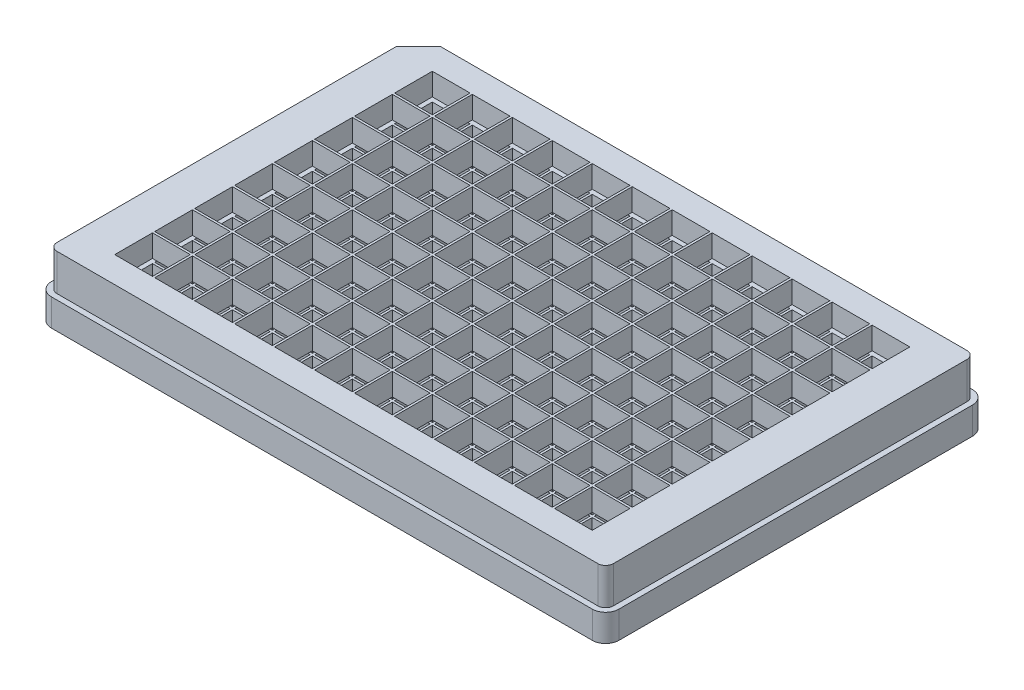
SolidWorks part; units mm, degrees
ref_plane "Front Plane" through (0, 0, 0) normal (0, 0, 1) x (1, 0, 0)
ref_plane "Top Plane" through (0, 0, 0) normal (0, 1, 0) x (1, 0, 0)
ref_plane "Right Plane" through (0, 0, 0) normal (1, 0, 0) x (0, 0, -1)
sketch "Sketch1" plane through (0, 0, 0) normal (0, 1, 0) x (1, 0, 0)
  line L0 (-63.875, -42.8) -> (63.875, 42.8) construction
  line L1 (-63.875, -42.8) -> (63.875, -42.8)
  line L2 (-63.875, -42.8) -> (-63.875, 42.8)
  line L3 (-63.875, 42.8) -> (63.875, 42.8)
  line L4 (63.875, -42.8) -> (63.875, 42.8)
  point P4 (0, 0)
  dimension "D1" = 85.6
  dimension "D2" = 127.75
extrude "Boss-Extrude1" add sketch "Sketch1" along normal blind 14.35
fillet "Fillet1" radius 3 4 edges at (-63.875, 7.175, -42.8) (-63.875, 7.175, 42.8) (63.875, 7.175, 42.8) (63.875, 7.175, -42.8)
sketch "Sketch3" plane through (0, 14.35, 0) normal (0, 1, 0) x (1, 0, 0)
  line L0 (-63.875, 39.8) -> (-63.875, -39.8) construction
  line L1 (60.875, 42.8) -> (-60.875, 42.8) construction
  line L2 (63.875, -39.8) -> (63.875, 39.8) construction
  line L3 (-60.875, -42.8) -> (60.875, -42.8) construction
  line L4 (-63.875, 39.8) -> (-63.875, -39.8)
  line L5 (60.875, 42.8) -> (-60.875, 42.8)
  line L6 (63.875, -39.8) -> (63.875, 39.8)
  line L7 (-60.875, -42.8) -> (60.875, -42.8)
  line L8 (-62.625, 36.6003) -> (-62.625, -39.8)
  line L9 (-60.875, -41.55) -> (60.875, -41.55)
  line L10 (62.625, -39.8) -> (62.625, 39.8)
  line L11 (60.875, 41.55) -> (-57.6753, 41.55)
  line L12 (-62.625, 36.6003) -> (-57.6753, 41.55)
  line L14 (-62.625, 39.8) -> (-62.625, -39.8) construction
  line L15 (60.875, 41.55) -> (-60.875, 41.55) construction
  arc A0 (-60.875, 42.8) -> (-63.875, 39.8) centre (-60.875, 39.8) ccw construction
  arc A1 (63.875, 39.8) -> (60.875, 42.8) centre (60.875, 39.8) ccw construction
  arc A2 (60.875, -42.8) -> (63.875, -39.8) centre (60.875, -39.8) ccw construction
  arc A3 (-63.875, -39.8) -> (-60.875, -42.8) centre (-60.875, -39.8) ccw construction
  arc A4 (-60.875, 42.8) -> (-63.875, 39.8) centre (-60.875, 39.8) ccw
  arc A5 (63.875, 39.8) -> (60.875, 42.8) centre (60.875, 39.8) ccw
  arc A6 (60.875, -42.8) -> (63.875, -39.8) centre (60.875, -39.8) ccw
  arc A7 (-63.875, -39.8) -> (-60.875, -42.8) centre (-60.875, -39.8) ccw
  arc A8 (-62.625, -39.8) -> (-60.875, -41.55) centre (-60.875, -39.8) ccw
  arc A9 (60.875, -41.55) -> (62.625, -39.8) centre (60.875, -39.8) ccw
  arc A10 (62.625, 39.8) -> (60.875, 41.55) centre (60.875, 39.8) ccw
  arc A16 (-60.875, 41.55) -> (-62.625, 39.8) centre (-60.875, 39.8) ccw construction
  dimension "D2" = 135
  dimension "D3" = 7
  dimension "D1" = 1.25
extrude "Cut-Flange" cut sketch "Sketch3" against normal offset from surface (8.25 mm away) 6.1 up to face at (0, 0, 0)
sketch "Sketch4" plane through (0, 14.35, 0) normal (0, 1, 0) x (1, 0, 0)
  line L0 (-63.875, 39.8) -> (-63.875, -39.8) construction
  line L1 (63.875, 39.8) -> (63.875, -39.8) construction
  line L2 (-49.495, 41.55) -> (-49.495, -41.55) construction
  line L3 (60.875, 41.55) -> (-57.6753, 41.55) construction
  line L4 (-60.875, -41.55) -> (60.875, -41.55) construction
  line L5 (49.505, 41.55) -> (49.505, -41.55) construction
  line L6 (-63.875, 31.56) -> (63.875, 31.56) construction
  line L7 (60.875, 42.8) -> (-60.875, 42.8) construction
  line L8 (-63.875, -31.44) -> (63.875, -31.44) construction
  line L9 (-44.745, 27.31) -> (-36.245, 27.31)
  line L10 (-53.745, 27.31) -> (-45.245, 27.31)
  line L11 (-53.745, 27.31) -> (-53.745, 35.81)
  line L12 (-53.745, 35.81) -> (-45.245, 35.81)
  line L13 (-45.245, 27.31) -> (-45.245, 35.81)
  line L14 (-53.745, 27.31) -> (-45.245, 35.81) construction
  line L15 (-53.745, 35.81) -> (-45.245, 27.31) construction
  line L16 (-44.745, 27.31) -> (-44.745, 35.81)
  line L17 (-44.745, 35.81) -> (-36.245, 35.81)
  line L18 (-36.245, 27.31) -> (-36.245, 35.81)
  line L19 (-44.745, 27.31) -> (-36.245, 35.81) construction
  line L20 (-44.745, 35.81) -> (-36.245, 27.31) construction
  line L21 (-35.745, 27.31) -> (-27.245, 27.31)
  line L22 (-35.745, 27.31) -> (-35.745, 35.81)
  line L23 (-35.745, 35.81) -> (-27.245, 35.81)
  line L24 (-27.245, 27.31) -> (-27.245, 35.81)
  line L25 (-35.745, 27.31) -> (-27.245, 35.81) construction
  line L26 (-35.745, 35.81) -> (-27.245, 27.31) construction
  line L27 (-26.745, 27.31) -> (-18.245, 27.31)
  line L28 (-26.745, 27.31) -> (-26.745, 35.81)
  line L29 (-26.745, 35.81) -> (-18.245, 35.81)
  line L30 (-18.245, 27.31) -> (-18.245, 35.81)
  line L31 (-26.745, 27.31) -> (-18.245, 35.81) construction
  line L32 (-26.745, 35.81) -> (-18.245, 27.31) construction
  line L33 (-17.745, 27.31) -> (-9.245, 27.31)
  line L34 (-17.745, 27.31) -> (-17.745, 35.81)
  line L35 (-17.745, 35.81) -> (-9.245, 35.81)
  line L36 (-9.245, 27.31) -> (-9.245, 35.81)
  line L37 (-17.745, 27.31) -> (-9.245, 35.81) construction
  line L38 (-17.745, 35.81) -> (-9.245, 27.31) construction
  line L39 (-8.745, 27.31) -> (-0.245, 27.31)
  line L40 (-8.745, 27.31) -> (-8.745, 35.81)
  line L41 (-8.745, 35.81) -> (-0.245, 35.81)
  line L42 (-0.245, 27.31) -> (-0.245, 35.81)
  line L43 (-8.745, 27.31) -> (-0.245, 35.81) construction
  line L44 (-8.745, 35.81) -> (-0.245, 27.31) construction
  line L45 (0.255, 27.31) -> (8.755, 27.31)
  line L46 (0.255, 27.31) -> (0.255, 35.81)
  line L47 (0.255, 35.81) -> (8.755, 35.81)
  line L48 (8.755, 27.31) -> (8.755, 35.81)
  line L49 (0.255, 27.31) -> (8.755, 35.81) construction
  line L50 (0.255, 35.81) -> (8.755, 27.31) construction
  line L51 (9.255, 27.31) -> (17.755, 27.31)
  line L52 (9.255, 27.31) -> (9.255, 35.81)
  line L53 (9.255, 35.81) -> (17.755, 35.81)
  line L54 (17.755, 27.31) -> (17.755, 35.81)
  line L55 (9.255, 27.31) -> (17.755, 35.81) construction
  line L56 (9.255, 35.81) -> (17.755, 27.31) construction
  line L57 (18.255, 27.31) -> (26.755, 27.31)
  line L58 (18.255, 27.31) -> (18.255, 35.81)
  line L59 (18.255, 35.81) -> (26.755, 35.81)
  line L60 (26.755, 27.31) -> (26.755, 35.81)
  line L61 (18.255, 27.31) -> (26.755, 35.81) construction
  line L62 (18.255, 35.81) -> (26.755, 27.31) construction
  line L63 (27.255, 27.31) -> (35.755, 27.31)
  line L64 (27.255, 27.31) -> (27.255, 35.81)
  line L65 (27.255, 35.81) -> (35.755, 35.81)
  line L66 (35.755, 27.31) -> (35.755, 35.81)
  line L67 (27.255, 27.31) -> (35.755, 35.81) construction
  line L68 (27.255, 35.81) -> (35.755, 27.31) construction
  line L69 (36.255, 27.31) -> (44.755, 27.31)
  line L70 (36.255, 27.31) -> (36.255, 35.81)
  line L71 (36.255, 35.81) -> (44.755, 35.81)
  line L72 (44.755, 27.31) -> (44.755, 35.81)
  line L73 (36.255, 27.31) -> (44.755, 35.81) construction
  line L74 (36.255, 35.81) -> (44.755, 27.31) construction
  line L75 (45.255, 27.31) -> (53.755, 27.31)
  line L76 (45.255, 27.31) -> (45.255, 35.81)
  line L77 (45.255, 35.81) -> (53.755, 35.81)
  line L78 (53.755, 27.31) -> (53.755, 35.81)
  line L79 (45.255, 27.31) -> (53.755, 35.81) construction
  line L80 (45.255, 35.81) -> (53.755, 27.31) construction
  line L81 (-44.745, 18.31) -> (-36.245, 18.31)
  line L82 (-44.745, 18.31) -> (-44.745, 26.81)
  line L83 (-44.745, 26.81) -> (-36.245, 26.81)
  line L84 (-36.245, 18.31) -> (-36.245, 26.81)
  line L85 (-44.745, 18.31) -> (-36.245, 26.81) construction
  line L86 (-44.745, 26.81) -> (-36.245, 18.31) construction
  line L87 (-35.745, 18.31) -> (-27.245, 18.31)
  line L88 (-35.745, 18.31) -> (-35.745, 26.81)
  line L89 (-35.745, 26.81) -> (-27.245, 26.81)
  line L90 (-27.245, 18.31) -> (-27.245, 26.81)
  line L91 (-35.745, 18.31) -> (-27.245, 26.81) construction
  line L92 (-35.745, 26.81) -> (-27.245, 18.31) construction
  line L93 (-26.745, 18.31) -> (-18.245, 18.31)
  line L94 (-26.745, 18.31) -> (-26.745, 26.81)
  line L95 (-26.745, 26.81) -> (-18.245, 26.81)
  line L96 (-18.245, 18.31) -> (-18.245, 26.81)
  line L97 (-26.745, 18.31) -> (-18.245, 26.81) construction
  line L98 (-26.745, 26.81) -> (-18.245, 18.31) construction
  line L99 (-17.745, 18.31) -> (-9.245, 18.31)
  line L100 (-17.745, 18.31) -> (-17.745, 26.81)
  line L101 (-17.745, 26.81) -> (-9.245, 26.81)
  line L102 (-9.245, 18.31) -> (-9.245, 26.81)
  line L103 (-17.745, 18.31) -> (-9.245, 26.81) construction
  line L104 (-17.745, 26.81) -> (-9.245, 18.31) construction
  line L105 (-8.745, 18.31) -> (-0.245, 18.31)
  line L106 (-8.745, 18.31) -> (-8.745, 26.81)
  line L107 (-8.745, 26.81) -> (-0.245, 26.81)
  line L108 (-0.245, 18.31) -> (-0.245, 26.81)
  line L109 (-8.745, 18.31) -> (-0.245, 26.81) construction
  line L110 (-8.745, 26.81) -> (-0.245, 18.31) construction
  line L111 (0.255, 18.31) -> (8.755, 18.31)
  line L112 (0.255, 18.31) -> (0.255, 26.81)
  line L113 (0.255, 26.81) -> (8.755, 26.81)
  line L114 (8.755, 18.31) -> (8.755, 26.81)
  line L115 (0.255, 18.31) -> (8.755, 26.81) construction
  line L116 (0.255, 26.81) -> (8.755, 18.31) construction
  line L117 (9.255, 18.31) -> (17.755, 18.31)
  line L118 (9.255, 18.31) -> (9.255, 26.81)
  line L119 (9.255, 26.81) -> (17.755, 26.81)
  line L120 (17.755, 18.31) -> (17.755, 26.81)
  line L121 (9.255, 18.31) -> (17.755, 26.81) construction
  line L122 (9.255, 26.81) -> (17.755, 18.31) construction
  line L123 (18.255, 18.31) -> (26.755, 18.31)
  line L124 (18.255, 18.31) -> (18.255, 26.81)
  line L125 (18.255, 26.81) -> (26.755, 26.81)
  line L126 (26.755, 18.31) -> (26.755, 26.81)
  line L127 (18.255, 18.31) -> (26.755, 26.81) construction
  line L128 (18.255, 26.81) -> (26.755, 18.31) construction
  line L129 (27.255, 18.31) -> (35.755, 18.31)
  line L130 (27.255, 18.31) -> (27.255, 26.81)
  line L131 (27.255, 26.81) -> (35.755, 26.81)
  line L132 (35.755, 18.31) -> (35.755, 26.81)
  line L133 (27.255, 18.31) -> (35.755, 26.81) construction
  line L134 (27.255, 26.81) -> (35.755, 18.31) construction
  line L135 (36.255, 18.31) -> (44.755, 18.31)
  line L136 (36.255, 18.31) -> (36.255, 26.81)
  line L137 (36.255, 26.81) -> (44.755, 26.81)
  line L138 (44.755, 18.31) -> (44.755, 26.81)
  line L139 (36.255, 18.31) -> (44.755, 26.81) construction
  line L140 (36.255, 26.81) -> (44.755, 18.31) construction
  line L141 (45.255, 18.31) -> (53.755, 18.31)
  line L142 (45.255, 18.31) -> (45.255, 26.81)
  line L143 (45.255, 26.81) -> (53.755, 26.81)
  line L144 (53.755, 18.31) -> (53.755, 26.81)
  line L145 (45.255, 18.31) -> (53.755, 26.81) construction
  line L146 (45.255, 26.81) -> (53.755, 18.31) construction
  line L147 (-44.745, 9.31) -> (-36.245, 9.31)
  line L148 (-44.745, 9.31) -> (-44.745, 17.81)
  line L149 (-44.745, 17.81) -> (-36.245, 17.81)
  line L150 (-36.245, 9.31) -> (-36.245, 17.81)
  line L151 (-44.745, 9.31) -> (-36.245, 17.81) construction
  line L152 (-44.745, 17.81) -> (-36.245, 9.31) construction
  line L153 (-35.745, 9.31) -> (-27.245, 9.31)
  line L154 (-35.745, 9.31) -> (-35.745, 17.81)
  line L155 (-35.745, 17.81) -> (-27.245, 17.81)
  line L156 (-27.245, 9.31) -> (-27.245, 17.81)
  line L157 (-35.745, 9.31) -> (-27.245, 17.81) construction
  line L158 (-35.745, 17.81) -> (-27.245, 9.31) construction
  line L159 (-26.745, 9.31) -> (-18.245, 9.31)
  line L160 (-26.745, 9.31) -> (-26.745, 17.81)
  line L161 (-26.745, 17.81) -> (-18.245, 17.81)
  line L162 (-18.245, 9.31) -> (-18.245, 17.81)
  line L163 (-26.745, 9.31) -> (-18.245, 17.81) construction
  line L164 (-26.745, 17.81) -> (-18.245, 9.31) construction
  line L165 (-17.745, 9.31) -> (-9.245, 9.31)
  line L166 (-17.745, 9.31) -> (-17.745, 17.81)
  line L167 (-17.745, 17.81) -> (-9.245, 17.81)
  line L168 (-9.245, 9.31) -> (-9.245, 17.81)
  line L169 (-17.745, 9.31) -> (-9.245, 17.81) construction
  line L170 (-17.745, 17.81) -> (-9.245, 9.31) construction
  line L171 (-8.745, 9.31) -> (-0.245, 9.31)
  line L172 (-8.745, 9.31) -> (-8.745, 17.81)
  line L173 (-8.745, 17.81) -> (-0.245, 17.81)
  line L174 (-0.245, 9.31) -> (-0.245, 17.81)
  line L175 (-8.745, 9.31) -> (-0.245, 17.81) construction
  line L176 (-8.745, 17.81) -> (-0.245, 9.31) construction
  line L177 (0.255, 9.31) -> (8.755, 9.31)
  line L178 (0.255, 9.31) -> (0.255, 17.81)
  line L179 (0.255, 17.81) -> (8.755, 17.81)
  line L180 (8.755, 9.31) -> (8.755, 17.81)
  line L181 (0.255, 9.31) -> (8.755, 17.81) construction
  line L182 (0.255, 17.81) -> (8.755, 9.31) construction
  line L183 (9.255, 9.31) -> (17.755, 9.31)
  line L184 (9.255, 9.31) -> (9.255, 17.81)
  line L185 (9.255, 17.81) -> (17.755, 17.81)
  line L186 (17.755, 9.31) -> (17.755, 17.81)
  line L187 (9.255, 9.31) -> (17.755, 17.81) construction
  line L188 (9.255, 17.81) -> (17.755, 9.31) construction
  line L189 (18.255, 9.31) -> (26.755, 9.31)
  line L190 (18.255, 9.31) -> (18.255, 17.81)
  line L191 (18.255, 17.81) -> (26.755, 17.81)
  line L192 (26.755, 9.31) -> (26.755, 17.81)
  line L193 (18.255, 9.31) -> (26.755, 17.81) construction
  line L194 (18.255, 17.81) -> (26.755, 9.31) construction
  line L195 (27.255, 9.31) -> (35.755, 9.31)
  line L196 (27.255, 9.31) -> (27.255, 17.81)
  line L197 (27.255, 17.81) -> (35.755, 17.81)
  line L198 (35.755, 9.31) -> (35.755, 17.81)
  line L199 (27.255, 9.31) -> (35.755, 17.81) construction
  line L200 (27.255, 17.81) -> (35.755, 9.31) construction
  line L201 (36.255, 9.31) -> (44.755, 9.31)
  line L202 (36.255, 9.31) -> (36.255, 17.81)
  line L203 (36.255, 17.81) -> (44.755, 17.81)
  line L204 (44.755, 9.31) -> (44.755, 17.81)
  line L205 (36.255, 9.31) -> (44.755, 17.81) construction
  line L206 (36.255, 17.81) -> (44.755, 9.31) construction
  line L207 (45.255, 9.31) -> (53.755, 9.31)
  line L208 (45.255, 9.31) -> (45.255, 17.81)
  line L209 (45.255, 17.81) -> (53.755, 17.81)
  line L210 (53.755, 9.31) -> (53.755, 17.81)
  line L211 (45.255, 9.31) -> (53.755, 17.81) construction
  line L212 (45.255, 17.81) -> (53.755, 9.31) construction
  line L213 (-44.745, 0.31) -> (-36.245, 0.31)
  line L214 (-44.745, 0.31) -> (-44.745, 8.81)
  line L215 (-44.745, 8.81) -> (-36.245, 8.81)
  line L216 (-36.245, 0.31) -> (-36.245, 8.81)
  line L217 (-44.745, 0.31) -> (-36.245, 8.81) construction
  line L218 (-44.745, 8.81) -> (-36.245, 0.31) construction
  line L219 (-35.745, 0.31) -> (-27.245, 0.31)
  line L220 (-35.745, 0.31) -> (-35.745, 8.81)
  line L221 (-35.745, 8.81) -> (-27.245, 8.81)
  line L222 (-27.245, 0.31) -> (-27.245, 8.81)
  line L223 (-35.745, 0.31) -> (-27.245, 8.81) construction
  line L224 (-35.745, 8.81) -> (-27.245, 0.31) construction
  line L225 (-26.745, 0.31) -> (-18.245, 0.31)
  line L226 (-26.745, 0.31) -> (-26.745, 8.81)
  line L227 (-26.745, 8.81) -> (-18.245, 8.81)
  line L228 (-18.245, 0.31) -> (-18.245, 8.81)
  line L229 (-26.745, 0.31) -> (-18.245, 8.81) construction
  line L230 (-26.745, 8.81) -> (-18.245, 0.31) construction
  line L231 (-17.745, 0.31) -> (-9.245, 0.31)
  line L232 (-17.745, 0.31) -> (-17.745, 8.81)
  line L233 (-17.745, 8.81) -> (-9.245, 8.81)
  line L234 (-9.245, 0.31) -> (-9.245, 8.81)
  line L235 (-17.745, 0.31) -> (-9.245, 8.81) construction
  line L236 (-17.745, 8.81) -> (-9.245, 0.31) construction
  line L237 (-8.745, 0.31) -> (-0.245, 0.31)
  line L238 (-8.745, 0.31) -> (-8.745, 8.81)
  line L239 (-8.745, 8.81) -> (-0.245, 8.81)
  line L240 (-0.245, 0.31) -> (-0.245, 8.81)
  line L241 (-8.745, 0.31) -> (-0.245, 8.81) construction
  line L242 (-8.745, 8.81) -> (-0.245, 0.31) construction
  line L243 (0.255, 0.31) -> (8.755, 0.31)
  line L244 (0.255, 0.31) -> (0.255, 8.81)
  line L245 (0.255, 8.81) -> (8.755, 8.81)
  line L246 (8.755, 0.31) -> (8.755, 8.81)
  line L247 (0.255, 0.31) -> (8.755, 8.81) construction
  line L248 (0.255, 8.81) -> (8.755, 0.31) construction
  line L249 (9.255, 0.31) -> (17.755, 0.31)
  line L250 (9.255, 0.31) -> (9.255, 8.81)
  line L251 (9.255, 8.81) -> (17.755, 8.81)
  line L252 (17.755, 0.31) -> (17.755, 8.81)
  line L253 (9.255, 0.31) -> (17.755, 8.81) construction
  line L254 (9.255, 8.81) -> (17.755, 0.31) construction
  line L255 (18.255, 0.31) -> (26.755, 0.31)
  line L256 (18.255, 0.31) -> (18.255, 8.81)
  line L257 (18.255, 8.81) -> (26.755, 8.81)
  line L258 (26.755, 0.31) -> (26.755, 8.81)
  line L259 (18.255, 0.31) -> (26.755, 8.81) construction
  line L260 (18.255, 8.81) -> (26.755, 0.31) construction
  line L261 (27.255, 0.31) -> (35.755, 0.31)
  line L262 (27.255, 0.31) -> (27.255, 8.81)
  line L263 (27.255, 8.81) -> (35.755, 8.81)
  line L264 (35.755, 0.31) -> (35.755, 8.81)
  line L265 (27.255, 0.31) -> (35.755, 8.81) construction
  line L266 (27.255, 8.81) -> (35.755, 0.31) construction
  line L267 (36.255, 0.31) -> (44.755, 0.31)
  line L268 (36.255, 0.31) -> (36.255, 8.81)
  line L269 (36.255, 8.81) -> (44.755, 8.81)
  line L270 (44.755, 0.31) -> (44.755, 8.81)
  line L271 (36.255, 0.31) -> (44.755, 8.81) construction
  line L272 (36.255, 8.81) -> (44.755, 0.31) construction
  line L273 (45.255, 0.31) -> (53.755, 0.31)
  line L274 (45.255, 0.31) -> (45.255, 8.81)
  line L275 (45.255, 8.81) -> (53.755, 8.81)
  line L276 (53.755, 0.31) -> (53.755, 8.81)
  line L277 (45.255, 0.31) -> (53.755, 8.81) construction
  line L278 (45.255, 8.81) -> (53.755, 0.31) construction
  line L279 (-44.745, -8.69) -> (-36.245, -8.69)
  line L280 (-44.745, -8.69) -> (-44.745, -0.19)
  line L281 (-44.745, -0.19) -> (-36.245, -0.19)
  line L282 (-36.245, -8.69) -> (-36.245, -0.19)
  line L283 (-44.745, -8.69) -> (-36.245, -0.19) construction
  line L284 (-44.745, -0.19) -> (-36.245, -8.69) construction
  line L285 (-35.745, -8.69) -> (-27.245, -8.69)
  line L286 (-35.745, -8.69) -> (-35.745, -0.19)
  line L287 (-35.745, -0.19) -> (-27.245, -0.19)
  line L288 (-27.245, -8.69) -> (-27.245, -0.19)
  line L289 (-35.745, -8.69) -> (-27.245, -0.19) construction
  line L290 (-35.745, -0.19) -> (-27.245, -8.69) construction
  line L291 (-26.745, -8.69) -> (-18.245, -8.69)
  line L292 (-26.745, -8.69) -> (-26.745, -0.19)
  line L293 (-26.745, -0.19) -> (-18.245, -0.19)
  line L294 (-18.245, -8.69) -> (-18.245, -0.19)
  line L295 (-26.745, -8.69) -> (-18.245, -0.19) construction
  line L296 (-26.745, -0.19) -> (-18.245, -8.69) construction
  line L297 (-17.745, -8.69) -> (-9.245, -8.69)
  line L298 (-17.745, -8.69) -> (-17.745, -0.19)
  line L299 (-17.745, -0.19) -> (-9.245, -0.19)
  line L300 (-9.245, -8.69) -> (-9.245, -0.19)
  line L301 (-17.745, -8.69) -> (-9.245, -0.19) construction
  line L302 (-17.745, -0.19) -> (-9.245, -8.69) construction
  line L303 (-8.745, -8.69) -> (-0.245, -8.69)
  line L304 (-8.745, -8.69) -> (-8.745, -0.19)
  line L305 (-8.745, -0.19) -> (-0.245, -0.19)
  line L306 (-0.245, -8.69) -> (-0.245, -0.19)
  line L307 (-8.745, -8.69) -> (-0.245, -0.19) construction
  line L308 (-8.745, -0.19) -> (-0.245, -8.69) construction
  line L309 (0.255, -8.69) -> (8.755, -8.69)
  line L310 (0.255, -8.69) -> (0.255, -0.19)
  line L311 (0.255, -0.19) -> (8.755, -0.19)
  line L312 (8.755, -8.69) -> (8.755, -0.19)
  line L313 (0.255, -8.69) -> (8.755, -0.19) construction
  line L314 (0.255, -0.19) -> (8.755, -8.69) construction
  line L315 (9.255, -8.69) -> (17.755, -8.69)
  line L316 (9.255, -8.69) -> (9.255, -0.19)
  line L317 (9.255, -0.19) -> (17.755, -0.19)
  line L318 (17.755, -8.69) -> (17.755, -0.19)
  line L319 (9.255, -8.69) -> (17.755, -0.19) construction
  line L320 (9.255, -0.19) -> (17.755, -8.69) construction
  line L321 (18.255, -8.69) -> (26.755, -8.69)
  line L322 (18.255, -8.69) -> (18.255, -0.19)
  line L323 (18.255, -0.19) -> (26.755, -0.19)
  line L324 (26.755, -8.69) -> (26.755, -0.19)
  line L325 (18.255, -8.69) -> (26.755, -0.19) construction
  line L326 (18.255, -0.19) -> (26.755, -8.69) construction
  line L327 (27.255, -8.69) -> (35.755, -8.69)
  line L328 (27.255, -8.69) -> (27.255, -0.19)
  line L329 (27.255, -0.19) -> (35.755, -0.19)
  line L330 (35.755, -8.69) -> (35.755, -0.19)
  line L331 (27.255, -8.69) -> (35.755, -0.19) construction
  line L332 (27.255, -0.19) -> (35.755, -8.69) construction
  line L333 (36.255, -8.69) -> (44.755, -8.69)
  line L334 (36.255, -8.69) -> (36.255, -0.19)
  line L335 (36.255, -0.19) -> (44.755, -0.19)
  line L336 (44.755, -8.69) -> (44.755, -0.19)
  line L337 (36.255, -8.69) -> (44.755, -0.19) construction
  line L338 (36.255, -0.19) -> (44.755, -8.69) construction
  line L339 (45.255, -8.69) -> (53.755, -8.69)
  line L340 (45.255, -8.69) -> (45.255, -0.19)
  line L341 (45.255, -0.19) -> (53.755, -0.19)
  line L342 (53.755, -8.69) -> (53.755, -0.19)
  line L343 (45.255, -8.69) -> (53.755, -0.19) construction
  line L344 (45.255, -0.19) -> (53.755, -8.69) construction
  line L345 (-44.745, -17.69) -> (-36.245, -17.69)
  line L346 (-44.745, -17.69) -> (-44.745, -9.19)
  line L347 (-44.745, -9.19) -> (-36.245, -9.19)
  line L348 (-36.245, -17.69) -> (-36.245, -9.19)
  line L349 (-44.745, -17.69) -> (-36.245, -9.19) construction
  line L350 (-44.745, -9.19) -> (-36.245, -17.69) construction
  line L351 (-35.745, -17.69) -> (-27.245, -17.69)
  line L352 (-35.745, -17.69) -> (-35.745, -9.19)
  line L353 (-35.745, -9.19) -> (-27.245, -9.19)
  line L354 (-27.245, -17.69) -> (-27.245, -9.19)
  line L355 (-35.745, -17.69) -> (-27.245, -9.19) construction
  line L356 (-35.745, -9.19) -> (-27.245, -17.69) construction
  line L357 (-26.745, -17.69) -> (-18.245, -17.69)
  line L358 (-26.745, -17.69) -> (-26.745, -9.19)
  line L359 (-26.745, -9.19) -> (-18.245, -9.19)
  line L360 (-18.245, -17.69) -> (-18.245, -9.19)
  line L361 (-26.745, -17.69) -> (-18.245, -9.19) construction
  line L362 (-26.745, -9.19) -> (-18.245, -17.69) construction
  line L363 (-17.745, -17.69) -> (-9.245, -17.69)
  line L364 (-17.745, -17.69) -> (-17.745, -9.19)
  line L365 (-17.745, -9.19) -> (-9.245, -9.19)
  line L366 (-9.245, -17.69) -> (-9.245, -9.19)
  line L367 (-17.745, -17.69) -> (-9.245, -9.19) construction
  line L368 (-17.745, -9.19) -> (-9.245, -17.69) construction
  line L369 (-8.745, -17.69) -> (-0.245, -17.69)
  line L370 (-8.745, -17.69) -> (-8.745, -9.19)
  line L371 (-8.745, -9.19) -> (-0.245, -9.19)
  line L372 (-0.245, -17.69) -> (-0.245, -9.19)
  line L373 (-8.745, -17.69) -> (-0.245, -9.19) construction
  line L374 (-8.745, -9.19) -> (-0.245, -17.69) construction
  line L375 (0.255, -17.69) -> (8.755, -17.69)
  line L376 (0.255, -17.69) -> (0.255, -9.19)
  line L377 (0.255, -9.19) -> (8.755, -9.19)
  line L378 (8.755, -17.69) -> (8.755, -9.19)
  line L379 (0.255, -17.69) -> (8.755, -9.19) construction
  line L380 (0.255, -9.19) -> (8.755, -17.69) construction
  line L381 (9.255, -17.69) -> (17.755, -17.69)
  line L382 (9.255, -17.69) -> (9.255, -9.19)
  line L383 (9.255, -9.19) -> (17.755, -9.19)
  line L384 (17.755, -17.69) -> (17.755, -9.19)
  line L385 (9.255, -17.69) -> (17.755, -9.19) construction
  line L386 (9.255, -9.19) -> (17.755, -17.69) construction
  line L387 (18.255, -17.69) -> (26.755, -17.69)
  line L388 (18.255, -17.69) -> (18.255, -9.19)
  line L389 (18.255, -9.19) -> (26.755, -9.19)
  line L390 (26.755, -17.69) -> (26.755, -9.19)
  line L391 (18.255, -17.69) -> (26.755, -9.19) construction
  line L392 (18.255, -9.19) -> (26.755, -17.69) construction
  line L393 (27.255, -17.69) -> (35.755, -17.69)
  line L394 (27.255, -17.69) -> (27.255, -9.19)
  line L395 (27.255, -9.19) -> (35.755, -9.19)
  line L396 (35.755, -17.69) -> (35.755, -9.19)
  line L397 (27.255, -17.69) -> (35.755, -9.19) construction
  line L398 (27.255, -9.19) -> (35.755, -17.69) construction
  line L399 (36.255, -17.69) -> (44.755, -17.69)
  line L400 (36.255, -17.69) -> (36.255, -9.19)
  line L401 (36.255, -9.19) -> (44.755, -9.19)
  line L402 (44.755, -17.69) -> (44.755, -9.19)
  line L403 (36.255, -17.69) -> (44.755, -9.19) construction
  line L404 (36.255, -9.19) -> (44.755, -17.69) construction
  line L405 (45.255, -17.69) -> (53.755, -17.69)
  line L406 (45.255, -17.69) -> (45.255, -9.19)
  line L407 (45.255, -9.19) -> (53.755, -9.19)
  line L408 (53.755, -17.69) -> (53.755, -9.19)
  line L409 (45.255, -17.69) -> (53.755, -9.19) construction
  line L410 (45.255, -9.19) -> (53.755, -17.69) construction
  line L411 (-44.745, -26.69) -> (-36.245, -26.69)
  line L412 (-44.745, -26.69) -> (-44.745, -18.19)
  line L413 (-44.745, -18.19) -> (-36.245, -18.19)
  line L414 (-36.245, -26.69) -> (-36.245, -18.19)
  line L415 (-44.745, -26.69) -> (-36.245, -18.19) construction
  line L416 (-44.745, -18.19) -> (-36.245, -26.69) construction
  line L417 (-35.745, -26.69) -> (-27.245, -26.69)
  line L418 (-35.745, -26.69) -> (-35.745, -18.19)
  line L419 (-35.745, -18.19) -> (-27.245, -18.19)
  line L420 (-27.245, -26.69) -> (-27.245, -18.19)
  line L421 (-35.745, -26.69) -> (-27.245, -18.19) construction
  line L422 (-35.745, -18.19) -> (-27.245, -26.69) construction
  line L423 (-26.745, -26.69) -> (-18.245, -26.69)
  line L424 (-26.745, -26.69) -> (-26.745, -18.19)
  line L425 (-26.745, -18.19) -> (-18.245, -18.19)
  line L426 (-18.245, -26.69) -> (-18.245, -18.19)
  line L427 (-26.745, -26.69) -> (-18.245, -18.19) construction
  line L428 (-26.745, -18.19) -> (-18.245, -26.69) construction
  line L429 (-17.745, -26.69) -> (-9.245, -26.69)
  line L430 (-17.745, -26.69) -> (-17.745, -18.19)
  line L431 (-17.745, -18.19) -> (-9.245, -18.19)
  line L432 (-9.245, -26.69) -> (-9.245, -18.19)
  line L433 (-17.745, -26.69) -> (-9.245, -18.19) construction
  line L434 (-17.745, -18.19) -> (-9.245, -26.69) construction
  line L435 (-8.745, -26.69) -> (-0.245, -26.69)
  line L436 (-8.745, -26.69) -> (-8.745, -18.19)
  line L437 (-8.745, -18.19) -> (-0.245, -18.19)
  line L438 (-0.245, -26.69) -> (-0.245, -18.19)
  line L439 (-8.745, -26.69) -> (-0.245, -18.19) construction
  line L440 (-8.745, -18.19) -> (-0.245, -26.69) construction
  line L441 (0.255, -26.69) -> (8.755, -26.69)
  line L442 (0.255, -26.69) -> (0.255, -18.19)
  line L443 (0.255, -18.19) -> (8.755, -18.19)
  line L444 (8.755, -26.69) -> (8.755, -18.19)
  line L445 (0.255, -26.69) -> (8.755, -18.19) construction
  line L446 (0.255, -18.19) -> (8.755, -26.69) construction
  line L447 (9.255, -26.69) -> (17.755, -26.69)
  line L448 (9.255, -26.69) -> (9.255, -18.19)
  line L449 (9.255, -18.19) -> (17.755, -18.19)
  line L450 (17.755, -26.69) -> (17.755, -18.19)
  line L451 (9.255, -26.69) -> (17.755, -18.19) construction
  line L452 (9.255, -18.19) -> (17.755, -26.69) construction
  line L453 (18.255, -26.69) -> (26.755, -26.69)
  line L454 (18.255, -26.69) -> (18.255, -18.19)
  line L455 (18.255, -18.19) -> (26.755, -18.19)
  line L456 (26.755, -26.69) -> (26.755, -18.19)
  line L457 (18.255, -26.69) -> (26.755, -18.19) construction
  line L458 (18.255, -18.19) -> (26.755, -26.69) construction
  line L459 (27.255, -26.69) -> (35.755, -26.69)
  line L460 (27.255, -26.69) -> (27.255, -18.19)
  line L461 (27.255, -18.19) -> (35.755, -18.19)
  line L462 (35.755, -26.69) -> (35.755, -18.19)
  line L463 (27.255, -26.69) -> (35.755, -18.19) construction
  line L464 (27.255, -18.19) -> (35.755, -26.69) construction
  line L465 (36.255, -26.69) -> (44.755, -26.69)
  line L466 (36.255, -26.69) -> (36.255, -18.19)
  line L467 (36.255, -18.19) -> (44.755, -18.19)
  line L468 (44.755, -26.69) -> (44.755, -18.19)
  line L469 (36.255, -26.69) -> (44.755, -18.19) construction
  line L470 (36.255, -18.19) -> (44.755, -26.69) construction
  line L471 (45.255, -26.69) -> (53.755, -26.69)
  line L472 (45.255, -26.69) -> (45.255, -18.19)
  line L473 (45.255, -18.19) -> (53.755, -18.19)
  line L474 (53.755, -26.69) -> (53.755, -18.19)
  line L475 (45.255, -26.69) -> (53.755, -18.19) construction
  line L476 (45.255, -18.19) -> (53.755, -26.69) construction
  line L477 (-44.745, -35.69) -> (-36.245, -35.69)
  line L478 (-44.745, -35.69) -> (-44.745, -27.19)
  line L479 (-44.745, -27.19) -> (-36.245, -27.19)
  line L480 (-36.245, -35.69) -> (-36.245, -27.19)
  line L481 (-44.745, -35.69) -> (-36.245, -27.19) construction
  line L482 (-44.745, -27.19) -> (-36.245, -35.69) construction
  line L483 (-35.745, -35.69) -> (-27.245, -35.69)
  line L484 (-35.745, -35.69) -> (-35.745, -27.19)
  line L485 (-35.745, -27.19) -> (-27.245, -27.19)
  line L486 (-27.245, -35.69) -> (-27.245, -27.19)
  line L487 (-35.745, -35.69) -> (-27.245, -27.19) construction
  line L488 (-35.745, -27.19) -> (-27.245, -35.69) construction
  line L489 (-26.745, -35.69) -> (-18.245, -35.69)
  line L490 (-26.745, -35.69) -> (-26.745, -27.19)
  line L491 (-26.745, -27.19) -> (-18.245, -27.19)
  line L492 (-18.245, -35.69) -> (-18.245, -27.19)
  line L493 (-26.745, -35.69) -> (-18.245, -27.19) construction
  line L494 (-26.745, -27.19) -> (-18.245, -35.69) construction
  line L495 (-17.745, -35.69) -> (-9.245, -35.69)
  line L496 (-17.745, -35.69) -> (-17.745, -27.19)
  line L497 (-17.745, -27.19) -> (-9.245, -27.19)
  line L498 (-9.245, -35.69) -> (-9.245, -27.19)
  line L499 (-17.745, -35.69) -> (-9.245, -27.19) construction
  line L500 (-17.745, -27.19) -> (-9.245, -35.69) construction
  line L501 (-8.745, -35.69) -> (-0.245, -35.69)
  line L502 (-8.745, -35.69) -> (-8.745, -27.19)
  line L503 (-8.745, -27.19) -> (-0.245, -27.19)
  line L504 (-0.245, -35.69) -> (-0.245, -27.19)
  line L505 (-8.745, -35.69) -> (-0.245, -27.19) construction
  line L506 (-8.745, -27.19) -> (-0.245, -35.69) construction
  line L507 (0.255, -35.69) -> (8.755, -35.69)
  line L508 (0.255, -35.69) -> (0.255, -27.19)
  line L509 (0.255, -27.19) -> (8.755, -27.19)
  line L510 (8.755, -35.69) -> (8.755, -27.19)
  line L511 (0.255, -35.69) -> (8.755, -27.19) construction
  line L512 (0.255, -27.19) -> (8.755, -35.69) construction
  line L513 (9.255, -35.69) -> (17.755, -35.69)
  line L514 (9.255, -35.69) -> (9.255, -27.19)
  line L515 (9.255, -27.19) -> (17.755, -27.19)
  line L516 (17.755, -35.69) -> (17.755, -27.19)
  line L517 (9.255, -35.69) -> (17.755, -27.19) construction
  line L518 (9.255, -27.19) -> (17.755, -35.69) construction
  line L519 (18.255, -35.69) -> (26.755, -35.69)
  line L520 (18.255, -35.69) -> (18.255, -27.19)
  line L521 (18.255, -27.19) -> (26.755, -27.19)
  line L522 (26.755, -35.69) -> (26.755, -27.19)
  line L523 (18.255, -35.69) -> (26.755, -27.19) construction
  line L524 (18.255, -27.19) -> (26.755, -35.69) construction
  line L525 (27.255, -35.69) -> (35.755, -35.69)
  line L526 (27.255, -35.69) -> (27.255, -27.19)
  line L527 (27.255, -27.19) -> (35.755, -27.19)
  line L528 (35.755, -35.69) -> (35.755, -27.19)
  line L529 (27.255, -35.69) -> (35.755, -27.19) construction
  line L530 (27.255, -27.19) -> (35.755, -35.69) construction
  line L531 (36.255, -35.69) -> (44.755, -35.69)
  line L532 (36.255, -35.69) -> (36.255, -27.19)
  line L533 (36.255, -27.19) -> (44.755, -27.19)
  line L534 (44.755, -35.69) -> (44.755, -27.19)
  line L535 (36.255, -35.69) -> (44.755, -27.19) construction
  line L536 (36.255, -27.19) -> (44.755, -35.69) construction
  line L537 (45.255, -35.69) -> (53.755, -35.69)
  line L538 (45.255, -35.69) -> (45.255, -27.19)
  line L539 (45.255, -27.19) -> (53.755, -27.19)
  line L540 (53.755, -35.69) -> (53.755, -27.19)
  line L541 (45.255, -35.69) -> (53.755, -27.19) construction
  line L542 (45.255, -27.19) -> (53.755, -35.69) construction
  line L543 (-53.745, 18.31) -> (-45.245, 18.31)
  line L544 (-53.745, 18.31) -> (-53.745, 26.81)
  line L545 (-53.745, 26.81) -> (-45.245, 26.81)
  line L546 (-45.245, 18.31) -> (-45.245, 26.81)
  line L547 (-53.745, 18.31) -> (-45.245, 26.81) construction
  line L548 (-53.745, 26.81) -> (-45.245, 18.31) construction
  line L549 (-53.745, 9.31) -> (-45.245, 9.31)
  line L550 (-53.745, 9.31) -> (-53.745, 17.81)
  line L551 (-53.745, 17.81) -> (-45.245, 17.81)
  line L552 (-45.245, 9.31) -> (-45.245, 17.81)
  line L553 (-53.745, 9.31) -> (-45.245, 17.81) construction
  line L554 (-53.745, 17.81) -> (-45.245, 9.31) construction
  line L555 (-53.745, 0.31) -> (-45.245, 0.31)
  line L556 (-53.745, 0.31) -> (-53.745, 8.81)
  line L557 (-53.745, 8.81) -> (-45.245, 8.81)
  line L558 (-45.245, 0.31) -> (-45.245, 8.81)
  line L559 (-53.745, 0.31) -> (-45.245, 8.81) construction
  line L560 (-53.745, 8.81) -> (-45.245, 0.31) construction
  line L561 (-53.745, -8.69) -> (-45.245, -8.69)
  line L562 (-53.745, -8.69) -> (-53.745, -0.19)
  line L563 (-53.745, -0.19) -> (-45.245, -0.19)
  line L564 (-45.245, -8.69) -> (-45.245, -0.19)
  line L565 (-53.745, -8.69) -> (-45.245, -0.19) construction
  line L566 (-53.745, -0.19) -> (-45.245, -8.69) construction
  line L567 (-53.745, -17.69) -> (-45.245, -17.69)
  line L568 (-53.745, -17.69) -> (-53.745, -9.19)
  line L569 (-53.745, -9.19) -> (-45.245, -9.19)
  line L570 (-45.245, -17.69) -> (-45.245, -9.19)
  line L571 (-53.745, -17.69) -> (-45.245, -9.19) construction
  line L572 (-53.745, -9.19) -> (-45.245, -17.69) construction
  line L573 (-53.745, -26.69) -> (-45.245, -26.69)
  line L574 (-53.745, -26.69) -> (-53.745, -18.19)
  line L575 (-53.745, -18.19) -> (-45.245, -18.19)
  line L576 (-45.245, -26.69) -> (-45.245, -18.19)
  line L577 (-53.745, -26.69) -> (-45.245, -18.19) construction
  line L578 (-53.745, -18.19) -> (-45.245, -26.69) construction
  line L579 (-53.745, -35.69) -> (-45.245, -35.69)
  line L580 (-53.745, -35.69) -> (-53.745, -27.19)
  line L581 (-53.745, -27.19) -> (-45.245, -27.19)
  line L582 (-45.245, -35.69) -> (-45.245, -27.19)
  line L583 (-53.745, -35.69) -> (-45.245, -27.19) construction
  line L584 (-53.745, -27.19) -> (-45.245, -35.69) construction
  point P22 (-49.495, 31.56)
  point P23 (-49.495, 31.56)
  point P30 (-40.495, 31.56)
  point P31 (-40.495, 31.56)
  point P36 (-31.495, 31.56)
  point P37 (-31.495, 31.56)
  point P42 (-22.495, 31.56)
  point P43 (-22.495, 31.56)
  point P48 (-13.495, 31.56)
  point P49 (-13.495, 31.56)
  point P54 (-4.495, 31.56)
  point P55 (-4.495, 31.56)
  point P60 (4.505, 31.56)
  point P61 (4.505, 31.56)
  point P66 (13.505, 31.56)
  point P67 (13.505, 31.56)
  point P72 (22.505, 31.56)
  point P73 (22.505, 31.56)
  point P78 (31.505, 31.56)
  point P79 (31.505, 31.56)
  point P84 (40.505, 31.56)
  point P85 (40.505, 31.56)
  point P90 (49.505, 31.56)
  point P91 (49.505, 31.56)
  point P96 (-40.495, 22.56)
  point P97 (-40.495, 22.56)
  point P102 (-31.495, 22.56)
  point P103 (-31.495, 22.56)
  point P108 (-22.495, 22.56)
  point P109 (-22.495, 22.56)
  point P114 (-13.495, 22.56)
  point P115 (-13.495, 22.56)
  point P120 (-4.495, 22.56)
  point P121 (-4.495, 22.56)
  point P126 (4.505, 22.56)
  point P127 (4.505, 22.56)
  point P132 (13.505, 22.56)
  point P133 (13.505, 22.56)
  point P138 (22.505, 22.56)
  point P139 (22.505, 22.56)
  point P144 (31.505, 22.56)
  point P145 (31.505, 22.56)
  point P150 (40.505, 22.56)
  point P151 (40.505, 22.56)
  point P156 (49.505, 22.56)
  point P157 (49.505, 22.56)
  point P162 (-40.495, 13.56)
  point P163 (-40.495, 13.56)
  point P168 (-31.495, 13.56)
  point P169 (-31.495, 13.56)
  point P174 (-22.495, 13.56)
  point P175 (-22.495, 13.56)
  point P180 (-13.495, 13.56)
  point P181 (-13.495, 13.56)
  point P186 (-4.495, 13.56)
  point P187 (-4.495, 13.56)
  point P192 (4.505, 13.56)
  point P193 (4.505, 13.56)
  point P198 (13.505, 13.56)
  point P199 (13.505, 13.56)
  point P204 (22.505, 13.56)
  point P205 (22.505, 13.56)
  point P210 (31.505, 13.56)
  point P211 (31.505, 13.56)
  point P216 (40.505, 13.56)
  point P217 (40.505, 13.56)
  point P222 (49.505, 13.56)
  point P223 (49.505, 13.56)
  point P228 (-40.495, 4.56)
  point P229 (-40.495, 4.56)
  point P234 (-31.495, 4.56)
  point P235 (-31.495, 4.56)
  point P240 (-22.495, 4.56)
  point P241 (-22.495, 4.56)
  point P246 (-13.495, 4.56)
  point P247 (-13.495, 4.56)
  point P252 (-4.495, 4.56)
  point P253 (-4.495, 4.56)
  point P258 (4.505, 4.56)
  point P259 (4.505, 4.56)
  point P264 (13.505, 4.56)
  point P265 (13.505, 4.56)
  point P270 (22.505, 4.56)
  point P271 (22.505, 4.56)
  point P276 (31.505, 4.56)
  point P277 (31.505, 4.56)
  point P282 (40.505, 4.56)
  point P283 (40.505, 4.56)
  point P288 (49.505, 4.56)
  point P289 (49.505, 4.56)
  point P294 (-40.495, -4.44)
  point P295 (-40.495, -4.44)
  point P300 (-31.495, -4.44)
  point P301 (-31.495, -4.44)
  point P306 (-22.495, -4.44)
  point P307 (-22.495, -4.44)
  point P312 (-13.495, -4.44)
  point P313 (-13.495, -4.44)
  point P318 (-4.495, -4.44)
  point P319 (-4.495, -4.44)
  point P324 (4.505, -4.44)
  point P325 (4.505, -4.44)
  point P330 (13.505, -4.44)
  point P331 (13.505, -4.44)
  point P336 (22.505, -4.44)
  point P337 (22.505, -4.44)
  point P342 (31.505, -4.44)
  point P343 (31.505, -4.44)
  point P348 (40.505, -4.44)
  point P349 (40.505, -4.44)
  point P354 (49.505, -4.44)
  point P355 (49.505, -4.44)
  point P360 (-40.495, -13.44)
  point P361 (-40.495, -13.44)
  point P366 (-31.495, -13.44)
  point P367 (-31.495, -13.44)
  point P372 (-22.495, -13.44)
  point P373 (-22.495, -13.44)
  point P378 (-13.495, -13.44)
  point P379 (-13.495, -13.44)
  point P384 (-4.495, -13.44)
  point P385 (-4.495, -13.44)
  point P390 (4.505, -13.44)
  point P391 (4.505, -13.44)
  point P396 (13.505, -13.44)
  point P397 (13.505, -13.44)
  point P402 (22.505, -13.44)
  point P403 (22.505, -13.44)
  point P408 (31.505, -13.44)
  point P409 (31.505, -13.44)
  point P414 (40.505, -13.44)
  point P415 (40.505, -13.44)
  point P420 (49.505, -13.44)
  point P421 (49.505, -13.44)
  point P426 (-40.495, -22.44)
  point P427 (-40.495, -22.44)
  point P432 (-31.495, -22.44)
  point P433 (-31.495, -22.44)
  point P438 (-22.495, -22.44)
  point P439 (-22.495, -22.44)
  point P444 (-13.495, -22.44)
  point P445 (-13.495, -22.44)
  point P450 (-4.495, -22.44)
  point P451 (-4.495, -22.44)
  point P456 (4.505, -22.44)
  point P457 (4.505, -22.44)
  point P462 (13.505, -22.44)
  point P463 (13.505, -22.44)
  point P468 (22.505, -22.44)
  point P469 (22.505, -22.44)
  point P474 (31.505, -22.44)
  point P475 (31.505, -22.44)
  point P480 (40.505, -22.44)
  point P481 (40.505, -22.44)
  point P486 (49.505, -22.44)
  point P487 (49.505, -22.44)
  point P492 (-40.495, -31.44)
  point P493 (-40.495, -31.44)
  point P498 (-31.495, -31.44)
  point P499 (-31.495, -31.44)
  point P504 (-22.495, -31.44)
  point P505 (-22.495, -31.44)
  point P510 (-13.495, -31.44)
  point P511 (-13.495, -31.44)
  point P516 (-4.495, -31.44)
  point P517 (-4.495, -31.44)
  point P522 (4.505, -31.44)
  point P523 (4.505, -31.44)
  point P528 (13.505, -31.44)
  point P529 (13.505, -31.44)
  point P534 (22.505, -31.44)
  point P535 (22.505, -31.44)
  point P540 (31.505, -31.44)
  point P541 (31.505, -31.44)
  point P546 (40.505, -31.44)
  point P547 (40.505, -31.44)
  point P552 (49.505, -31.44)
  point P553 (49.505, -31.44)
  point P558 (-49.495, 22.56)
  point P559 (-49.495, 22.56)
  point P564 (-49.495, 13.56)
  point P565 (-49.495, 13.56)
  point P570 (-49.495, 4.56)
  point P571 (-49.495, 4.56)
  point P576 (-49.495, -4.44)
  point P577 (-49.495, -4.44)
  point P582 (-49.495, -13.44)
  point P583 (-49.495, -13.44)
  point P588 (-49.495, -22.44)
  point P589 (-49.495, -22.44)
  point P594 (-49.495, -31.44)
  point P595 (-49.495, -31.44)
  dimension "D1" = 14.38
  dimension "D2" = 99
  dimension "D3" = 11.24
  dimension "D4" = 63
  dimension "D5" = 8.5
  dimension "D6" = 8.5
  dimension "D7" = 12
  dimension "D8" = 8
sketch "Sketch5" plane through (-62.625, 0, 0) normal (-1, 0, 0) x (0, 0, 1)
  line L0 (0, 0) -> (0, 21.1352) construction
  line L1 (-41.55, 6.1) -> (-41.55, 14.35) construction
  line L2 (-40.05, 8.35) -> (40.05, 8.35)
  line L3 (-40.05, 8.35) -> (-40.05, 9.35)
  line L4 (-40.05, 9.35) -> (40.05, 9.35)
  line L5 (40.05, 8.35) -> (40.05, 9.35)
  line L6 (-40.05, 8.35) -> (40.05, 9.35) construction
  line L7 (-40.05, 9.35) -> (40.05, 8.35) construction
  line L8 (-41.55, 14.35) -> (41.55, 14.35) construction
  point P3 (0, 8.85)
  dimension "D1" = 1
  dimension "D2" = 1.5
  dimension "D3" = 5
extrude "Cut-PaperSlot" cut sketch "Sketch5" against normal offset from surface (123.75 mm away) 1.5 up to face at (62.625, 10.225, 0)
sketch "Sketch6" plane through (0, 14.35, 0) normal (0, 1, 0) x (1, 0, 0)
  line L3 (-57.6753, 37.55) -> (-61.6753, 37.55)
  line L4 (-57.6753, 41.55) -> (-62.625, 36.6003) construction
  line L5 (-60.875, -37.55) -> (-62.625, -37.55)
  line L6 (-60.875, -37.55) -> (58.625, -37.55)
  line L7 (58.625, -37.55) -> (58.625, 37.55)
  line L8 (58.625, 37.55) -> (-57.6753, 37.55)
  line L9 (-60.875, -37.55) -> (58.625, -37.55)
  line L10 (58.625, -37.55) -> (58.625, 37.55)
  line L11 (58.625, 37.55) -> (-57.6753, 37.55)
  line L12 (-62.625, 36.6003) -> (-62.625, -39.8) construction
  line L13 (-62.625, -37.55) -> (-62.625, 36.6003)
  line L14 (-62.625, 36.6003) -> (-61.6753, 37.55)
  dimension "D1" = 4
extrude "Cut-Extrude1" cut sketch "Sketch4" against normal blind 25
